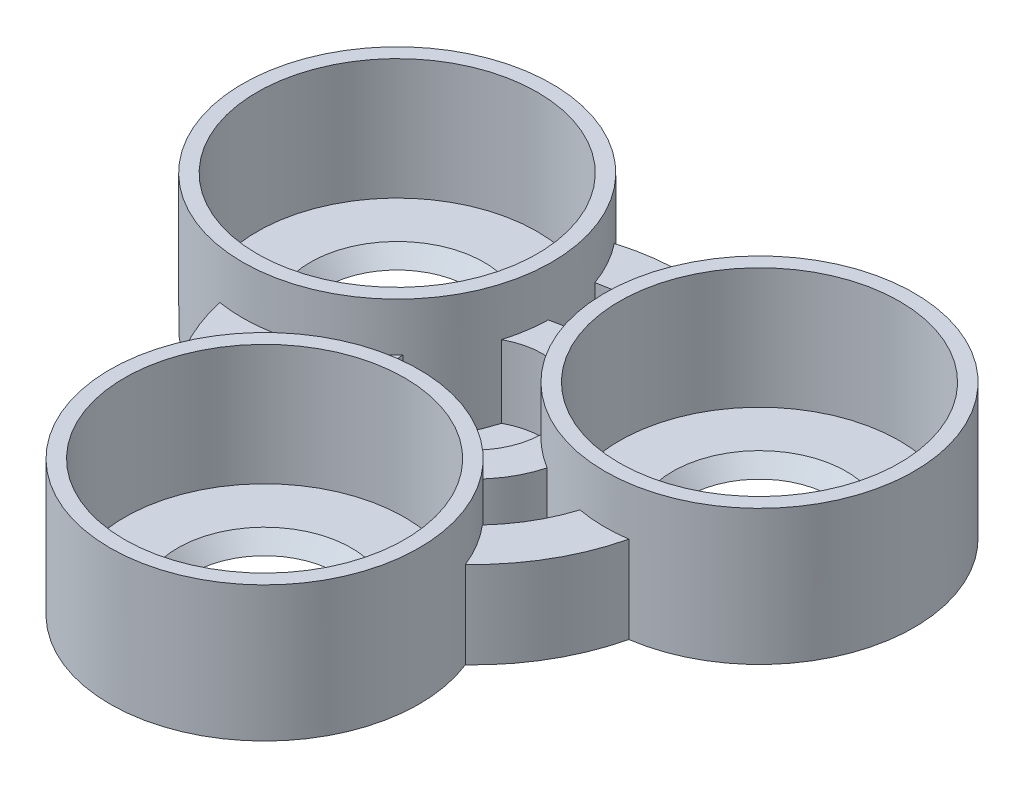
SolidWorks part; units mm, degrees
ref_plane "前视基准面" through (0, 0, 0) normal (0, 0, 1) x (1, 0, 0)
ref_plane "上视基准面" through (0, 0, 0) normal (0, 1, 0) x (1, 0, 0)
ref_plane "右视基准面" through (0, 0, 0) normal (1, 0, 0) x (0, 0, -1)
other "Configuration Table"
sketch "草图1" plane through (0, 0, 0) normal (0, 1, 0) x (1, 0, 0)
  line L0 (0, 0) -> (75, 0) construction
  line L1 (0, 0) -> (37.5, -64.9519) construction
  line L2 (75, 0) -> (37.5, -64.9519) construction
  circle A0 centre (0, 0) radius 28 construction
  circle A1 centre (75, 0) radius 28 construction
  circle A2 centre (37.5, -64.9519) radius 28 construction
  circle A4 centre (37.5, -21.6506) radius 43.3013 construction
  circle A5 centre (75, 0) radius 32
  circle A6 centre (37.5, -64.9519) radius 32
  circle A7 centre (0, 0) radius 32
  circle A8 centre (37.5, -21.6506) radius 33.3013 construction
  arc A9 (30.1147, 10.8214) -> (44.8853, 10.8214) centre (37.5, -21.6506) cw
  arc A10 (25.1077, 19.8395) -> (49.8923, 19.8395) centre (37.5, -21.6506) cw
  arc A11 (-5.1764, -31.5785) -> (7.564, -53.6456) centre (37.5, -21.6506) ccw
  arc A12 (5.6858, -31.4908) -> (13.071, -44.2825) centre (37.5, -21.6506) ccw
  arc A13 (79.6277, -31.6636) -> (67.2353, -53.1278) centre (37.5, -21.6506) cw
  arc A14 (69.3142, -31.4908) -> (61.929, -44.2825) centre (37.5, -21.6506) cw
  circle A15 centre (37.5, -21.6506) radius 21.6506
  dimension "D1" = 56
  dimension "D3" = 56
  dimension "D6" = 56
  dimension "D7" = 4
  dimension "D8" = 4
  dimension "D9" = 4
  dimension "D10" = 10
  dimension "D2" = 75
  dimension "D4" = 60
  dimension "D5" = 75
extrude "凸台-拉伸1" add sketch "草图1" along normal blind 3 contours A10 A7 A9 A5 | A7 | A5 | A12 A7 A11 A6 | A6 | A5 A14 A6 A13 | A15 region at (76.6996, 0, -0.9813) region at (37.5, 0, -16.6619) region at (70.6796, 0, 40.8069) region at (-1.6996, 0, -0.9813) region at (37.5, 0, 66.9144) region at (4.067, 0, 40.9532)
sketch "草图2" plane through (0, 3, 0) normal (0, 1, 0) x (1, 0, 0)
  circle A0 centre (0, 0) radius 32
  circle A1 centre (0, 0) radius 29
  circle A2 centre (37.5, -64.9519) radius 32
  circle A3 centre (75, 0) radius 32
  circle A4 centre (37.5, -64.9519) radius 29
  circle A5 centre (75, 0) radius 29
  dimension "D1" = 64
  dimension "D2" = 64
  dimension "D3" = 64
extrude "凸台-拉伸2" add sketch "草图2" along normal blind 25
sketch "草图3" plane through (0, 0, 0) normal (0, -1, 0) x (1, 0, 0)
  line L0 (37.5, 21.6506) -> (0, 0) construction
  line L1 (37.5, 64.9519) -> (37.5, 21.6506) construction
  line L2 (37.5, 21.6506) -> (75, 0) construction
  circle A0 centre (37.5, 64.9519) radius 15
  circle A1 centre (75, 0) radius 15
  circle A2 centre (0, 0) radius 15
  dimension "D1" = 30
  dimension "D2" = 30
  dimension "D3" = 30
extrude "切除-拉伸1" cut sketch "草图3" against normal up to next
chamfer "倒角1" distance 3 angle 45 3 edges at (37.5, 3, 79.9519) (75, 3, 15) (0, 3, 15)
sketch "草图10" plane through (0, 3, 0) normal (0, 1, 0) x (1, 0, 0)
  line L0 (37.5, -21.6506) -> (44.5, -21.6506) construction
  line L1 (37.5, -21.6506) -> (37.5, -14.6506) construction
  line L2 (37.5, -21.6506) -> (30.5, -21.6506) construction
  line L3 (37.5, -21.6506) -> (37.5, -28.6506) construction
  line L4 (37.5, -64.9519) -> (37.5, -21.6506) construction
  circle A0 centre (44.5, -21.6506) radius 1.5
  circle A1 centre (37.5, -14.6506) radius 1.5
  circle A2 centre (30.5, -21.6506) radius 1.5
  circle A3 centre (37.5, -28.6506) radius 1.5
  circle A4 centre (37.5, -21.6506) radius 4
  dimension "D5" = 3
  dimension "D6" = 3
  dimension "D7" = 3
  dimension "D8" = 3
  dimension "D9" = 8
  dimension "D1" = 7
  dimension "D2" = 7
  dimension "D3" = 7
  dimension "D4" = 7
extrude "切除-拉伸4" cut sketch "草图10" against normal up to next
sketch "草图11" plane through (0, 3, 0) normal (0, 1, 0) x (1, 0, 0)
  arc A0 (44.9816, -33.8388) -> (51.7961, -22.0358) centre (37.5, -21.6506) ccw
  arc A1 (16.6129, -27.3498) -> (22.1209, -36.8898) centre (37.5, -21.6506) ccw
  arc A2 (16.6129, -27.3498) -> (31.9921, -0.7123) centre (0, 0) ccw construction
  arc A3 (16.6129, -27.3498) -> (23.2039, -22.0358) centre (0, 0) ccw
  arc A4 (43.0079, -0.7123) -> (58.3871, -27.3498) centre (75, 0) ccw construction
  arc A5 (43.0079, -0.7123) -> (44.3144, -9.0773) centre (75, 0) ccw
  arc A6 (52.8791, -36.8898) -> (22.1209, -36.8898) centre (37.5, -64.9519) ccw construction
  arc A7 (52.8791, -36.8898) -> (44.9816, -33.8388) centre (37.5, -64.9519) ccw
  arc A8 (43.0079, -0.7123) -> (31.9921, -0.7123) centre (37.5, -21.6506) ccw
  arc A9 (52.8791, -36.8898) -> (58.3871, -27.3498) centre (37.5, -21.6506) ccw
  arc A10 (23.2039, -22.0358) -> (30.0184, -33.8388) centre (37.5, -21.6506) ccw
  arc A11 (44.3144, -9.0773) -> (30.6856, -9.0773) centre (37.5, -21.6506) ccw
  arc A12 (30.6856, -9.0773) -> (31.9921, -0.7123) centre (0, 0) ccw
  arc A13 (51.7961, -22.0358) -> (58.3871, -27.3498) centre (75, 0) ccw
  arc A14 (30.0184, -33.8388) -> (22.1209, -36.8898) centre (37.5, -64.9519) ccw
  arc A19 (44.8853, 10.8214) -> (30.1147, 10.8214) centre (37.5, -21.6506) ccw
  arc A20 (49.8923, 19.8395) -> (44.8853, 10.8214) centre (75, 0) ccw
  arc A21 (49.8923, 19.8395) -> (25.1077, 19.8395) centre (37.5, -21.6506) ccw
  arc A22 (30.1147, 10.8214) -> (25.1077, 19.8395) centre (0, 0) ccw
  arc A23 (44.8853, 10.8214) -> (30.1147, 10.8214) centre (37.5, -21.6506) ccw
  arc A24 (49.8923, 19.8395) -> (44.8853, 10.8214) centre (75, 0) ccw
  arc A25 (49.8923, 19.8395) -> (25.1077, 19.8395) centre (37.5, -21.6506) ccw
  arc A26 (30.1147, 10.8214) -> (25.1077, 19.8395) centre (0, 0) ccw
  arc A27 (-5.1764, -31.5785) -> (7.564, -53.6456) centre (37.5, -21.6506) ccw
  arc A28 (13.071, -44.2825) -> (7.564, -53.6456) centre (37.5, -64.9519) ccw
  arc A29 (5.6858, -31.4908) -> (13.071, -44.2825) centre (37.5, -21.6506) ccw
  arc A30 (-5.1764, -31.5785) -> (5.6858, -31.4908) centre (0, 0) ccw
  arc A31 (-5.1764, -31.5785) -> (7.564, -53.6456) centre (37.5, -21.6506) ccw
  arc A32 (13.071, -44.2825) -> (7.564, -53.6456) centre (37.5, -64.9519) ccw
  arc A33 (5.6858, -31.4908) -> (13.071, -44.2825) centre (37.5, -21.6506) ccw
  arc A34 (-5.1764, -31.5785) -> (5.6858, -31.4908) centre (0, 0) ccw
  arc A35 (67.2353, -53.1278) -> (79.6277, -31.6636) centre (37.5, -21.6506) ccw
  arc A36 (69.3142, -31.4908) -> (79.6277, -31.6636) centre (75, 0) ccw
  arc A37 (61.929, -44.2825) -> (69.3142, -31.4908) centre (37.5, -21.6506) ccw
  arc A38 (67.2353, -53.1278) -> (61.929, -44.2825) centre (37.5, -64.9519) ccw
  arc A39 (67.2353, -53.1278) -> (79.6277, -31.6636) centre (37.5, -21.6506) ccw
  arc A40 (69.3142, -31.4908) -> (79.6277, -31.6636) centre (75, 0) ccw
  arc A41 (61.929, -44.2825) -> (69.3142, -31.4908) centre (37.5, -21.6506) ccw
  arc A42 (67.2353, -53.1278) -> (61.929, -44.2825) centre (37.5, -64.9519) ccw
  dimension "D1" = 0
  dimension "D2" = 0
  dimension "D3" = 0
extrude "凸台-拉伸3" add sketch "草图11" along normal blind 15
